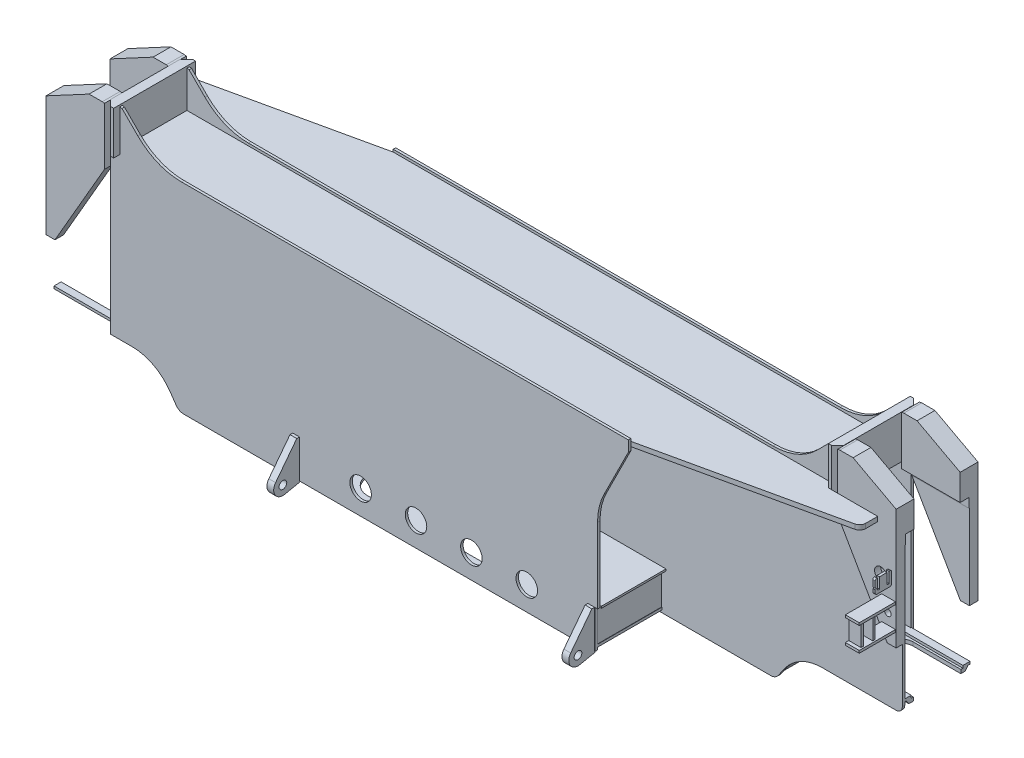
SolidWorks part; units mm, degrees
ref_plane "正面" through (0, 0, 0) normal (0, 0, 1) x (1, 0, 0)
ref_plane "平面" through (0, 0, 0) normal (0, 1, 0) x (1, 0, 0)
ref_plane "右側面" through (0, 0, 0) normal (1, 0, 0) x (0, 0, -1)
ref_plane "平面1" through (0, 0, 238) normal (0, 0, 1) x (1, 0, 0)
sketch "ｽｹｯﾁ2" plane through (0, 0, 238) normal (0, 0, 1) x (1, 0, 0)
  line L0 (20, 120) -> (259.781, 119.9998)
  line L1 (382.7741, 55.8641) -> (403.0452, 26.8271)
  line L2 (427.644, 13.9998) -> (2117.356, 13.9998)
  line L3 (2141.9548, 26.8271) -> (2162.2259, 55.8641)
  line L4 (2285.219, 119.9998) -> (2525, 120)
  line L5 (2545, 140) -> (2545, 315.36)
  line L6 (2545, 315.36) -> (2545, 706)
  line L7 (2545, 706) -> (2405, 781)
  line L8 (2405, 781) -> (2362, 781)
  line L9 (2362, 781) -> (2318, 774)
  line L10 (2318, 774) -> (2266.5789, 722.5791)
  line L11 (2125.157, 663.9999) -> (419.843, 663.9999)
  line L12 (278.4211, 722.5791) -> (227, 774)
  line L13 (227, 774) -> (183, 781)
  line L14 (183, 781) -> (140, 781)
  line L15 (140, 781) -> (0, 706)
  line L16 (0, 706) -> (0, 315.36)
  line L17 (0, 315.36) -> (0, 140)
  arc A0 (0, 140) -> (20, 120) centre (20, 140) ccw
  arc A1 (259.781, 119.9998) -> (382.7741, 55.8641) centre (259.781, -30) cw
  arc A2 (403.0452, 26.8271) -> (427.644, 13.9998) centre (427.644, 44) ccw
  arc A3 (2117.356, 13.9998) -> (2141.9548, 26.8271) centre (2117.356, 44) ccw
  arc A4 (2162.2259, 55.8641) -> (2285.219, 119.9998) centre (2285.219, -30) cw
  arc A5 (2525, 120) -> (2545, 140) centre (2525, 140) ccw
  arc A6 (2266.5789, 722.5791) -> (2125.157, 663.9999) centre (2125.157, 864) cw
  arc A7 (419.843, 663.9999) -> (278.4211, 722.5791) centre (419.843, 864) cw
extrude "ﾎﾞｽ - 押し出し1" add sketch "ｽｹｯﾁ2" along normal blind 8
sketch "ｽｹｯﾁ3" plane through (0, 0, 238) normal (0, 0, 1) x (1, 0, 0)
  line L0 (1072.5, 297) -> (1472.5, 297)
  line L1 (1472.5, 497) -> (1072.5, 497)
  circle A0 centre (972.5, 92) radius 35
  circle A1 centre (1272.5, 92) radius 35
  circle A2 centre (1572.5, 92) radius 35
  arc A3 (1472.5, 297) -> (1572.5, 397) centre (1472.5, 397) ccw
  arc A4 (1572.5, 397) -> (1472.5, 497) centre (1472.5, 397) ccw
  arc A5 (1072.5, 497) -> (972.5, 397) centre (1072.5, 397) ccw
  arc A6 (972.5, 397) -> (1072.5, 297) centre (1072.5, 397) ccw
sketch "ｽｹｯﾁ4" plane through (0, 0, 238) normal (0, 0, 1) x (1, 0, 0)
  line L0 (1072.5, 297) -> (1472.5, 297)
  line L1 (1472.5, 497) -> (1072.5, 497)
  circle A0 centre (972.5, 92) radius 35
  circle A1 centre (1272.5, 92) radius 35
  circle A2 centre (1572.5, 92) radius 35
  arc A3 (1472.5, 297) -> (1572.5, 397) centre (1472.5, 397) ccw
  arc A4 (1572.5, 397) -> (1472.5, 497) centre (1472.5, 397) ccw
  arc A5 (1072.5, 497) -> (972.5, 397) centre (1072.5, 397) ccw
  arc A6 (972.5, 397) -> (1072.5, 297) centre (1072.5, 397) ccw
extrude "ｶｯﾄ - 押し出し2" cut sketch "ｽｹｯﾁ4" along normal blind 8
ref_plane "平面2" through (0, 0, 20) normal (0, 0, 1) x (1, 0, 0)
sketch "ｽｹｯﾁ6" plane through (0, 0, 20) normal (0, 0, 1) x (1, 0, 0)
  line L0 (781, 14) -> (2117.356, 13.9998)
  line L1 (2141.9548, 26.8271) -> (2162.2259, 55.8641)
  line L2 (2285.219, 119.9998) -> (2355, 120)
  line L3 (2355, 120) -> (2355, 779.8864)
  line L4 (2355, 779.8864) -> (2318, 774)
  line L5 (2318, 774) -> (2266.5789, 722.5791)
  line L6 (2125.157, 663.9999) -> (672.5, 664)
  line L7 (672.5, 664) -> (672.5, 629)
  line L8 (672.5, 629) -> (751.3851, 471.2291)
  line L9 (772.4999, 381.786) -> (772.5, 138)
  line L10 (772.5, 138) -> (781, 138)
  line L11 (781, 138) -> (781, 14)
  arc A0 (2117.356, 13.9998) -> (2141.9548, 26.8271) centre (2117.356, 44) ccw
  arc A1 (2162.2259, 55.8641) -> (2285.219, 119.9998) centre (2285.219, -30) cw
  arc A2 (2266.5789, 722.5791) -> (2125.157, 663.9999) centre (2125.157, 864) cw
  arc A3 (751.3851, 471.2291) -> (772.4999, 381.786) centre (572.5, 381.786) cw
extrude "ﾎﾞｽ - 押し出し2" add sketch "ｽｹｯﾁ6" along normal blind 8
sketch "ｽｹｯﾁ7" plane through (0, 0, 20) normal (0, 0, 1) x (1, 0, 0)
  circle A0 centre (1002.5, 92) radius 35
  circle A1 centre (1182.5, 92) radius 35
  circle A2 centre (1362.5, 92) radius 35
  circle A3 centre (1542.5, 92) radius 35
sketch "ｽｹｯﾁ8" plane through (0, 0, 20) normal (0, 0, 1) x (1, 0, 0)
  circle A0 centre (1002.5, 92) radius 35
  circle A1 centre (1182.5, 92) radius 35
  circle A2 centre (1362.5, 92) radius 35
  circle A3 centre (1542.5, 92) radius 35
extrude "ｶｯﾄ - 押し出し4" cut sketch "ｽｹｯﾁ8" along normal blind 8
ref_plane "平面3" through (0, 0, 456) normal (0, 0, 1) x (1, 0, 0)
sketch "ｽｹｯﾁ10" plane through (0, 0, 456) normal (0, 0, 1) x (1, 0, 0)
  line L0 (1764, 14) -> (1764, 138)
  line L1 (1764, 138) -> (1772.5, 138)
  line L2 (1772.5, 138) -> (1772.5001, 381.786)
  line L3 (1793.6149, 471.2291) -> (1872.5, 629)
  line L4 (1872.5, 629) -> (1872.5, 664)
  line L5 (1872.5, 664) -> (419.843, 663.9999)
  line L6 (278.4211, 722.5791) -> (227, 774)
  line L7 (227, 774) -> (190, 779.8864)
  line L8 (190, 779.8864) -> (190, 120)
  line L9 (190, 120) -> (259.781, 119.9998)
  line L10 (382.7741, 55.8641) -> (403.0452, 26.8271)
  line L11 (427.644, 13.9998) -> (1764, 14)
  arc A0 (1772.5001, 381.786) -> (1793.6149, 471.2291) centre (1972.5, 381.786) cw
  arc A1 (419.843, 663.9999) -> (278.4211, 722.5791) centre (419.843, 864) cw
  arc A2 (259.781, 119.9998) -> (382.7741, 55.8641) centre (259.781, -30) cw
  arc A3 (403.0452, 26.8271) -> (427.644, 13.9998) centre (427.644, 44) ccw
extrude "ﾎﾞｽ - 押し出し3" add sketch "ｽｹｯﾁ10" along normal blind 8
sketch "ｽｹｯﾁ11" plane through (0, 0, 456) normal (0, 0, 1) x (1, 0, 0)
  circle A0 centre (1002.5, 92) radius 35
  circle A1 centre (1182.5, 92) radius 35
  circle A2 centre (1362.5, 92) radius 35
  circle A3 centre (1542.5, 92) radius 35
sketch "ｽｹｯﾁ12" plane through (0, 0, 456) normal (0, 0, 1) x (1, 0, 0)
  circle A0 centre (1002.5, 92) radius 35
  circle A1 centre (1182.5, 92) radius 35
  circle A2 centre (1362.5, 92) radius 35
  circle A3 centre (1542.5, 92) radius 35
extrude "ｶｯﾄ - 押し出し6" cut sketch "ｽｹｯﾁ12" along normal blind 8
ref_plane "平面4" through (0, 641, 0) normal (0, 1, 0) x (1, 0, 0)
sketch "ｽｹｯﾁ14" plane through (0, 641, 0) normal (0, 1, 0) x (1, 0, 0)
  line L0 (672.5, -28) -> (75.7206, -159.5325)
  line L1 (59.9974, -179.072) -> (60, -218)
  line L2 (60, -218) -> (220, -218)
  line L3 (220, -218) -> (220, -238)
  line L4 (220, -238) -> (2324.98, -238)
  line L5 (2324.98, -238) -> (2324.98, -28)
  line L6 (2324.98, -28) -> (672.5, -28)
  arc A0 (75.7206, -159.5325) -> (59.9974, -179.072) centre (80, -179.072) ccw
extrude "ﾎﾞｽ - 押し出し4" add sketch "ｽｹｯﾁ14" along normal blind 15
sketch "ｽｹｯﾁ15" plane through (0, 641, 0) normal (0, 1, 0) x (1, 0, 0)
  line L0 (1872.5, -456) -> (2469.2794, -324.4675)
  line L1 (2485.0026, -304.928) -> (2485, -266)
  line L2 (2485, -266) -> (2325, -266)
  line L3 (2325, -266) -> (2325, -246)
  line L4 (2325, -246) -> (220.02, -246)
  line L5 (220.02, -246) -> (220.02, -456)
  line L6 (220.02, -456) -> (1872.5, -456)
  arc A0 (2469.2794, -324.4675) -> (2485.0026, -304.928) centre (2465, -304.928) ccw
extrude "ﾎﾞｽ - 押し出し5" add sketch "ｽｹｯﾁ15" along normal blind 15
ref_plane "平面5" through (0, 22, 0) normal (0, 1, 0) x (1, 0, 0)
sketch "ｽｹｯﾁ17" plane through (0, 22, 0) normal (0, 1, 0) x (1, 0, 0)
  line L0 (781, -28) -> (2098.5, -28)
  line L1 (2098.5, -28) -> (2098.5, -238)
  line L2 (2098.5, -238) -> (781, -238)
  line L3 (781, -238) -> (781, -28)
extrude "ﾎﾞｽ - 押し出し6" add sketch "ｽｹｯﾁ17" along normal blind 8
sketch "ｽｹｯﾁ18" plane through (0, 22, 0) normal (0, 1, 0) x (1, 0, 0)
  line L0 (1202, -73) -> (1342, -73)
  line L1 (1342, -193) -> (1202, -193)
  circle A0 centre (972, -133) radius 60
  circle A1 centre (1572, -133) radius 60
  circle A2 centre (1942, -133) radius 60
  arc A3 (1342, -73) -> (1402, -133) centre (1342, -133) cw
  arc A4 (1402, -133) -> (1342, -193) centre (1342, -133) cw
  arc A5 (1202, -193) -> (1142, -133) centre (1202, -133) cw
  arc A6 (1142, -133) -> (1202, -73) centre (1202, -133) cw
sketch "ｽｹｯﾁ19" plane through (0, 22, 0) normal (0, 1, 0) x (1, 0, 0)
  line L0 (1202, -73) -> (1342, -73)
  line L1 (1342, -193) -> (1202, -193)
  circle A0 centre (972, -133) radius 60
  circle A1 centre (1572, -133) radius 60
  circle A2 centre (1942, -133) radius 60
  arc A3 (1342, -73) -> (1402, -133) centre (1342, -133) cw
  arc A4 (1402, -133) -> (1342, -193) centre (1342, -133) cw
  arc A5 (1202, -193) -> (1142, -133) centre (1202, -133) cw
  arc A6 (1142, -133) -> (1202, -73) centre (1202, -133) cw
extrude "ｶｯﾄ - 押し出し8" cut sketch "ｽｹｯﾁ19" along normal blind 8
sketch "ｽｹｯﾁ20" plane through (0, 22, 0) normal (0, 1, 0) x (1, 0, 0)
  line L0 (446.5, -246) -> (1764, -246)
  line L1 (1764, -246) -> (1764, -456)
  line L2 (1764, -456) -> (446.5, -456)
  line L3 (446.5, -456) -> (446.5, -246)
extrude "ﾎﾞｽ - 押し出し7" add sketch "ｽｹｯﾁ20" along normal blind 8
sketch "ｽｹｯﾁ21" plane through (0, 22, 0) normal (0, 1, 0) x (1, 0, 0)
  line L0 (1203, -291) -> (1343, -291)
  line L1 (1343, -411) -> (1203, -411)
  circle A0 centre (603, -351) radius 60
  circle A1 centre (973, -351) radius 60
  circle A2 centre (1573, -351) radius 60
  arc A3 (1343, -291) -> (1403, -351) centre (1343, -351) cw
  arc A4 (1403, -351) -> (1343, -411) centre (1343, -351) cw
  arc A5 (1203, -411) -> (1143, -351) centre (1203, -351) cw
  arc A6 (1143, -351) -> (1203, -291) centre (1203, -351) cw
extrude "ｶｯﾄ - 押し出し9" cut sketch "ｽｹｯﾁ21" along normal blind 8
ref_plane "平面6" through (1771.5, 0, 0) normal (1, 0, 0) x (0, 0, -1)
sketch "ｽｹｯﾁ23" plane through (1771.5, 0, 0) normal (1, 0, 0) x (0, 0, -1)
  line L0 (-27.7635, 29) -> (-40.0837, 28.97)
  line L1 (-40.0837, 28.97) -> (-63.75, 129.12)
  line L2 (-63.75, 129.12) -> (-53.77, 137.8)
  line L3 (-53.77, 137.8) -> (-53.4927, 137.8)
  line L4 (-53.4927, 137.8) -> (-27.7635, 29)
extrude "ﾎﾞｽ - 押し出し8" add sketch "ｽｹｯﾁ23" along normal blind 319
sketch "ｽｹｯﾁ24" plane through (1771.5, 0, 0) normal (1, 0, 0) x (0, 0, -1)
  line L0 (-212.5073, 137.8) -> (-212.23, 137.8)
  line L1 (-212.23, 137.8) -> (-202.25, 129.12)
  line L2 (-202.25, 129.12) -> (-225.9163, 28.97)
  line L3 (-225.9163, 28.97) -> (-238.2365, 29)
  line L4 (-238.2365, 29) -> (-212.5073, 137.8)
extrude "ﾎﾞｽ - 押し出し9" add sketch "ｽｹｯﾁ24" along normal blind 319
ref_plane "平面7" through (454.5, 0, 0) normal (1, 0, 0) x (0, 0, -1)
sketch "ｽｹｯﾁ26" plane through (454.5, 0, 0) normal (1, 0, 0) x (0, 0, -1)
  line L0 (-430.5073, 137.8) -> (-430.23, 137.8)
  line L1 (-430.23, 137.8) -> (-420.25, 129.12)
  line L2 (-420.25, 129.12) -> (-443.9163, 28.97)
  line L3 (-443.9163, 28.97) -> (-456.2365, 29)
  line L4 (-456.2365, 29) -> (-430.5073, 137.8)
extrude "ﾎﾞｽ - 押し出し10" add sketch "ｽｹｯﾁ26" along normal blind 319
sketch "ｽｹｯﾁ27" plane through (454.5, 0, 0) normal (1, 0, 0) x (0, 0, -1)
  line L0 (-245.7635, 29) -> (-258.0837, 28.97)
  line L1 (-258.0837, 28.97) -> (-281.75, 129.12)
  line L2 (-281.75, 129.12) -> (-271.77, 137.8)
  line L3 (-271.77, 137.8) -> (-271.4927, 137.8)
  line L4 (-271.4927, 137.8) -> (-245.7635, 29)
extrude "ﾎﾞｽ - 押し出し11" add sketch "ｽｹｯﾁ27" along normal blind 319
ref_plane "平面8" through (0, 138, 0) normal (0, 1, 0) x (1, 0, 0)
sketch "ｽｹｯﾁ29" plane through (0, 138, 0) normal (0, 1, 0) x (1, 0, 0)
  line L0 (768, -28) -> (1712, -28)
  line L1 (1712, -28) -> (1712, -238)
  line L2 (1712, -238) -> (768, -238)
  line L3 (768, -238) -> (768, -28)
extrude "ﾎﾞｽ - 押し出し12" add sketch "ｽｹｯﾁ29" along normal blind 6
sketch "ｽｹｯﾁ30" plane through (0, 138, 0) normal (0, 1, 0) x (1, 0, 0)
  line L0 (833, -246) -> (1777, -246)
  line L1 (1777, -246) -> (1777, -456)
  line L2 (1777, -456) -> (833, -456)
  line L3 (833, -456) -> (833, -246)
extrude "ﾎﾞｽ - 押し出し13" add sketch "ｽｹｯﾁ30" along normal blind 6
ref_plane "平面9" through (427.5, 0, 0) normal (1, 0, 0) x (0, 0, -1)
sketch "ｽｹｯﾁ32" plane through (427.5, 0, 0) normal (1, 0, 0) x (0, 0, -1)
  line L0 (-244, 22) -> (-458, 22)
  line L1 (-458, 22) -> (-458, 138)
  line L2 (-458, 138) -> (-244, 138)
  line L3 (-244, 138) -> (-244, 22)
extrude "ﾎﾞｽ - 押し出し14" add sketch "ｽｹｯﾁ32" along normal blind 19
sketch "ｽｹｯﾁ33" plane through (427.5, 0, 0) normal (1, 0, 0) x (0, 0, -1)
  circle A0 centre (-351, 80) radius 30
sketch "ｽｹｯﾁ34" plane through (427.5, 0, 0) normal (1, 0, 0) x (0, 0, -1)
  circle A0 centre (-351, 80) radius 30
extrude "ｶｯﾄ - 押し出し11" cut sketch "ｽｹｯﾁ34" along normal blind 19
ref_plane "平面10" through (2098.5, 0, 0) normal (1, 0, 0) x (0, 0, -1)
sketch "ｽｹｯﾁ36" plane through (2098.5, 0, 0) normal (1, 0, 0) x (0, 0, -1)
  line L0 (-26, 22) -> (-240, 22)
  line L1 (-240, 22) -> (-240, 138)
  line L2 (-240, 138) -> (-26, 138)
  line L3 (-26, 138) -> (-26, 22)
extrude "ﾎﾞｽ - 押し出し15" add sketch "ｽｹｯﾁ36" along normal blind 19
sketch "ｽｹｯﾁ37" plane through (2098.5, 0, 0) normal (1, 0, 0) x (0, 0, -1)
  circle A0 centre (-133, 80) radius 30
sketch "ｽｹｯﾁ38" plane through (2098.5, 0, 0) normal (1, 0, 0) x (0, 0, -1)
  circle A0 centre (-133, 80) radius 30
extrude "ｶｯﾄ - 押し出し13" cut sketch "ｽｹｯﾁ38" along normal blind 19
ref_plane "平面11" through (0, 0, 218) normal (0, 0, 1) x (1, 0, 0)
sketch "ｽｹｯﾁ40" plane through (0, 0, 218) normal (0, 0, 1) x (1, 0, 0)
  line L0 (0, 315.36) -> (29.1052, 315.36)
  line L1 (29.1052, 315.36) -> (190, 594.038)
  line L2 (190, 594.038) -> (190, 779.8864)
  line L3 (190, 779.8864) -> (183, 781)
  line L4 (183, 781) -> (140, 781)
  line L5 (140, 781) -> (0, 706)
  line L6 (0, 706) -> (0, 315.36)
extrude "ﾎﾞｽ - 押し出し16" add sketch "ｽｹｯﾁ40" along normal blind 20
ref_plane "平面12" through (0, 0, 464) normal (0, 0, 1) x (1, 0, 0)
sketch "ｽｹｯﾁ42" plane through (0, 0, 464) normal (0, 0, 1) x (1, 0, 0)
  line L0 (0, 315.36) -> (29.1052, 315.36)
  line L1 (29.1052, 315.36) -> (190, 594.038)
  line L2 (190, 594.038) -> (190, 779.8864)
  line L3 (190, 779.8864) -> (183, 781)
  line L4 (183, 781) -> (140, 781)
  line L5 (140, 781) -> (0, 706)
  line L6 (0, 706) -> (0, 315.36)
extrude "ﾎﾞｽ - 押し出し17" add sketch "ｽｹｯﾁ42" along normal blind 20
sketch "ｽｹｯﾁ43" plane through (0, 0, 0) normal (0, 0, 1) x (1, 0, 0)
  line L0 (2545, 315.36) -> (2545, 706)
  line L1 (2545, 706) -> (2405, 781)
  line L2 (2405, 781) -> (2362, 781)
  line L3 (2362, 781) -> (2355, 779.8864)
  line L4 (2355, 779.8864) -> (2355, 594.038)
  line L5 (2355, 594.038) -> (2515.8948, 315.36)
  line L6 (2515.8948, 315.36) -> (2545, 315.36)
extrude "ﾎﾞｽ - 押し出し18" add sketch "ｽｹｯﾁ43" along normal blind 20
ref_plane "平面13" through (0, 0, 246) normal (0, 0, 1) x (1, 0, 0)
sketch "ｽｹｯﾁ45" plane through (0, 0, 246) normal (0, 0, 1) x (1, 0, 0)
  line L0 (2545, 315.36) -> (2545, 706)
  line L1 (2545, 706) -> (2405, 781)
  line L2 (2405, 781) -> (2362, 781)
  line L3 (2362, 781) -> (2355, 779.8864)
  line L4 (2355, 779.8864) -> (2355, 594.038)
  line L5 (2355, 594.038) -> (2515.8948, 315.36)
  line L6 (2515.8948, 315.36) -> (2545, 315.36)
extrude "ﾎﾞｽ - 押し出し19" add sketch "ｽｹｯﾁ45" along normal blind 20
sketch "ｽｹｯﾁ46" plane through (0, 0, 218) normal (0, 0, 1) x (1, 0, 0)
  circle A0 centre (50, 499) radius 20.25
  circle A1 centre (27, 401.5) radius 10.5
sketch "ｽｹｯﾁ47" plane through (0, 0, 218) normal (0, 0, 1) x (1, 0, 0)
  circle A0 centre (50, 499) radius 20.25
  circle A1 centre (27, 401.5) radius 10.5
extrude "ｶｯﾄ - 押し出し15" cut sketch "ｽｹｯﾁ47" along normal blind 20
sketch "ｽｹｯﾁ48" plane through (0, 0, 246) normal (0, 0, 1) x (1, 0, 0)
  circle A0 centre (2495, 499) radius 20.25
  circle A1 centre (2518, 401.5) radius 10.5
sketch "ｽｹｯﾁ49" plane through (0, 0, 246) normal (0, 0, 1) x (1, 0, 0)
  circle A0 centre (2495, 499) radius 20.25
  circle A1 centre (2518, 401.5) radius 10.5
extrude "ｶｯﾄ - 押し出し17" cut sketch "ｽｹｯﾁ49" along normal blind 20
sketch "ｽｹｯﾁ50" plane through (0, 0, 20) normal (0, 0, 1) x (1, 0, 0)
  line L0 (2545, 315.36) -> (2545, 706)
  line L1 (2545, 706) -> (2405, 781)
  line L2 (2405, 781) -> (2362, 781)
  line L3 (2362, 781) -> (2355, 779.8864)
  line L4 (2355, 779.8864) -> (2355, 594.038)
  line L5 (2355, 594.038) -> (2515.8948, 315.36)
  line L6 (2515.8948, 315.36) -> (2545, 315.36)
extrude "ﾎﾞｽ - 押し出し20" add sketch "ｽｹｯﾁ50" along normal blind 8
sketch "ｽｹｯﾁ51" plane through (0, 0, 456) normal (0, 0, 1) x (1, 0, 0)
  line L0 (0, 315.36) -> (29.1052, 315.36)
  line L1 (29.1052, 315.36) -> (190, 594.038)
  line L2 (190, 594.038) -> (190, 779.8864)
  line L3 (190, 779.8864) -> (183, 781)
  line L4 (183, 781) -> (140, 781)
  line L5 (140, 781) -> (0, 706)
  line L6 (0, 706) -> (0, 315.36)
extrude "ﾎﾞｽ - 押し出し21" add sketch "ｽｹｯﾁ51" along normal blind 8
ref_plane "平面14" through (0, 0, 251) normal (0, 0, 1) x (1, 0, 0)
sketch "ｽｹｯﾁ53" plane through (0, 0, 251) normal (0, 0, 1) x (1, 0, 0)
  line L0 (0, 620.82) -> (190, 620.82)
  line L1 (190, 620.82) -> (190, 779.8864)
  line L2 (190, 779.8864) -> (183, 781)
  line L3 (183, 781) -> (140, 781)
  line L4 (140, 781) -> (0, 706)
  line L5 (0, 706) -> (0, 620.82)
extrude "ﾎﾞｽ - 押し出し22" add sketch "ｽｹｯﾁ53" along normal blind 25
ref_plane "平面15" through (0, 0, 426) normal (0, 0, 1) x (1, 0, 0)
sketch "ｽｹｯﾁ55" plane through (0, 0, 426) normal (0, 0, 1) x (1, 0, 0)
  line L0 (0, 620.82) -> (190, 620.82)
  line L1 (190, 620.82) -> (190, 779.8864)
  line L2 (190, 779.8864) -> (183, 781)
  line L3 (183, 781) -> (140, 781)
  line L4 (140, 781) -> (0, 706)
  line L5 (0, 706) -> (0, 620.82)
extrude "ﾎﾞｽ - 押し出し23" add sketch "ｽｹｯﾁ55" along normal blind 25
ref_plane "平面16" through (0, 0, 33) normal (0, 0, 1) x (1, 0, 0)
sketch "ｽｹｯﾁ57" plane through (0, 0, 33) normal (0, 0, 1) x (1, 0, 0)
  line L0 (2545, 620.82) -> (2545, 706)
  line L1 (2545, 706) -> (2405, 781)
  line L2 (2405, 781) -> (2362, 781)
  line L3 (2362, 781) -> (2355, 779.8864)
  line L4 (2355, 779.8864) -> (2355, 620.82)
  line L5 (2355, 620.82) -> (2545, 620.82)
extrude "ﾎﾞｽ - 押し出し24" add sketch "ｽｹｯﾁ57" along normal blind 25
ref_plane "平面17" through (0, 0, 208) normal (0, 0, 1) x (1, 0, 0)
sketch "ｽｹｯﾁ59" plane through (0, 0, 208) normal (0, 0, 1) x (1, 0, 0)
  line L0 (2545, 620.82) -> (2545, 706)
  line L1 (2545, 706) -> (2405, 781)
  line L2 (2405, 781) -> (2362, 781)
  line L3 (2362, 781) -> (2355, 779.8864)
  line L4 (2355, 779.8864) -> (2355, 620.82)
  line L5 (2355, 620.82) -> (2545, 620.82)
extrude "ﾎﾞｽ - 押し出し25" add sketch "ｽｹｯﾁ59" along normal blind 25
ref_plane "平面18" through (0, 0, 244) normal (0, 0, 1) x (1, 0, 0)
sketch "ｽｹｯﾁ61" plane through (0, 0, 244) normal (0, 0, 1) x (1, 0, 0)
  line L0 (0, 620.82) -> (190, 620.82)
  line L1 (190, 620.82) -> (190, 779.8864)
  line L2 (190, 779.8864) -> (183, 781)
  line L3 (183, 781) -> (140, 781)
  line L4 (140, 781) -> (0, 706)
  line L5 (0, 706) -> (0, 620.82)
extrude "ﾎﾞｽ - 押し出し26" add sketch "ｽｹｯﾁ61" along normal blind 7
sketch "ｽｹｯﾁ62" plane through (0, 0, 244) normal (0, 0, 1) x (1, 0, 0)
  line L0 (0, 590.821) -> (188.1427, 590.821)
  line L1 (188.1427, 590.821) -> (190, 594.038)
  line L2 (190, 594.038) -> (190, 620.82)
  line L3 (190, 620.82) -> (0, 620.82)
  line L4 (0, 620.82) -> (0, 590.821)
extrude "ﾎﾞｽ - 押し出し27" add sketch "ｽｹｯﾁ62" along normal blind 4
ref_plane "平面19" through (0, 0, 451) normal (0, 0, 1) x (1, 0, 0)
sketch "ｽｹｯﾁ64" plane through (0, 0, 451) normal (0, 0, 1) x (1, 0, 0)
  line L0 (0, 620.82) -> (190, 620.82)
  line L1 (190, 620.82) -> (190, 779.8864)
  line L2 (190, 779.8864) -> (183, 781)
  line L3 (183, 781) -> (140, 781)
  line L4 (140, 781) -> (0, 706)
  line L5 (0, 706) -> (0, 620.82)
extrude "ﾎﾞｽ - 押し出し28" add sketch "ｽｹｯﾁ64" along normal blind 7
ref_plane "平面20" through (0, 0, 454) normal (0, 0, 1) x (1, 0, 0)
sketch "ｽｹｯﾁ66" plane through (0, 0, 454) normal (0, 0, 1) x (1, 0, 0)
  line L0 (0, 590.821) -> (188.1427, 590.821)
  line L1 (188.1427, 590.821) -> (190, 594.038)
  line L2 (190, 594.038) -> (190, 620.82)
  line L3 (190, 620.82) -> (0, 620.82)
  line L4 (0, 620.82) -> (0, 590.821)
extrude "ﾎﾞｽ - 押し出し29" add sketch "ｽｹｯﾁ66" along normal blind 4
ref_plane "平面21" through (0, 0, 26) normal (0, 0, 1) x (1, 0, 0)
sketch "ｽｹｯﾁ68" plane through (0, 0, 26) normal (0, 0, 1) x (1, 0, 0)
  line L0 (2545, 620.82) -> (2545, 706)
  line L1 (2545, 706) -> (2405, 781)
  line L2 (2405, 781) -> (2362, 781)
  line L3 (2362, 781) -> (2355, 779.8864)
  line L4 (2355, 779.8864) -> (2355, 620.82)
  line L5 (2355, 620.82) -> (2545, 620.82)
extrude "ﾎﾞｽ - 押し出し30" add sketch "ｽｹｯﾁ68" along normal blind 7
sketch "ｽｹｯﾁ69" plane through (0, 0, 26) normal (0, 0, 1) x (1, 0, 0)
  line L0 (2545, 590.821) -> (2545, 620.82)
  line L1 (2545, 620.82) -> (2355, 620.82)
  line L2 (2355, 620.82) -> (2355, 594.038)
  line L3 (2355, 594.038) -> (2356.8573, 590.821)
  line L4 (2356.8573, 590.821) -> (2545, 590.821)
extrude "ﾎﾞｽ - 押し出し31" add sketch "ｽｹｯﾁ69" along normal blind 4
ref_plane "平面22" through (0, 0, 233) normal (0, 0, 1) x (1, 0, 0)
sketch "ｽｹｯﾁ71" plane through (0, 0, 233) normal (0, 0, 1) x (1, 0, 0)
  line L0 (2545, 620.82) -> (2545, 706)
  line L1 (2545, 706) -> (2405, 781)
  line L2 (2405, 781) -> (2362, 781)
  line L3 (2362, 781) -> (2355, 779.8864)
  line L4 (2355, 779.8864) -> (2355, 620.82)
  line L5 (2355, 620.82) -> (2545, 620.82)
extrude "ﾎﾞｽ - 押し出し32" add sketch "ｽｹｯﾁ71" along normal blind 7
ref_plane "平面23" through (0, 0, 236) normal (0, 0, 1) x (1, 0, 0)
sketch "ｽｹｯﾁ73" plane through (0, 0, 236) normal (0, 0, 1) x (1, 0, 0)
  line L0 (2545, 590.821) -> (2545, 620.82)
  line L1 (2545, 620.82) -> (2355, 620.82)
  line L2 (2355, 620.82) -> (2355, 594.038)
  line L3 (2355, 594.038) -> (2356.8573, 590.821)
  line L4 (2356.8573, 590.821) -> (2545, 590.821)
extrude "ﾎﾞｽ - 押し出し33" add sketch "ｽｹｯﾁ73" along normal blind 4
sketch "ｽｹｯﾁ74" plane through (0, 0, 0) normal (1, 0, 0) x (0, 0, -1)
  line L0 (-251.6, 150) -> (-450.4, 150)
  line L1 (-450.4, 150) -> (-450.4, 149)
  line L2 (-450.4, 149) -> (-442.698, 138)
  line L3 (-442.698, 138) -> (-259.302, 138)
  line L4 (-259.302, 138) -> (-251.6, 149)
  line L5 (-251.6, 149) -> (-251.6, 150)
extrude "ﾎﾞｽ - 押し出し34" add sketch "ｽｹｯﾁ74" along normal blind 833
sketch "ｽｹｯﾁ75" plane through (0, 138, 0) normal (0, 1, 0) x (1, 0, 0)
  line L0 (-10, -273.771) -> (155, -273.771)
  line L1 (195, -313.771) -> (195, -388.229)
  line L2 (155, -428.229) -> (-10, -428.229)
  line L3 (-10, -428.229) -> (-10, -273.771)
  arc A0 (155, -273.771) -> (195, -313.771) centre (155, -313.771) cw
  arc A1 (195, -388.229) -> (155, -428.229) centre (155, -388.229) cw
sketch "ｽｹｯﾁ76" plane through (0, 138, 0) normal (0, 1, 0) x (1, 0, 0)
  line L0 (-10, -273.771) -> (155, -273.771)
  line L1 (195, -313.771) -> (195, -388.229)
  line L2 (155, -428.229) -> (-10, -428.229)
  line L3 (-10, -428.229) -> (-10, -273.771)
  arc A0 (155, -273.771) -> (195, -313.771) centre (155, -313.771) cw
  arc A1 (195, -388.229) -> (155, -428.229) centre (155, -388.229) cw
extrude "ｶｯﾄ - 押し出し19" cut sketch "ｽｹｯﾁ76" along normal blind 12
ref_plane "平面24" through (2545, 0, 0) normal (1, 0, 0) x (0, 0, -1)
sketch "ｽｹｯﾁ78" plane through (2545, 0, 0) normal (1, 0, 0) x (0, 0, -1)
  line L0 (-232.4, 150) -> (-232.4, 149)
  line L1 (-232.4, 149) -> (-224.698, 138)
  line L2 (-224.698, 138) -> (-41.302, 138)
  line L3 (-41.302, 138) -> (-33.6, 149)
  line L4 (-33.6, 149) -> (-33.6, 150)
  line L5 (-33.6, 150) -> (-232.4, 150)
extrude "ﾎﾞｽ - 押し出し35" add sketch "ｽｹｯﾁ78" against normal blind 833
sketch "ｽｹｯﾁ79" plane through (0, 138, 0) normal (0, 1, 0) x (1, 0, 0)
  line L0 (2555, -210.229) -> (2390, -210.229)
  line L1 (2350, -170.229) -> (2350, -95.771)
  line L2 (2390, -55.771) -> (2555, -55.771)
  line L3 (2555, -55.771) -> (2555, -210.229)
  arc A0 (2390, -210.229) -> (2350, -170.229) centre (2390, -170.229) cw
  arc A1 (2350, -95.771) -> (2390, -55.771) centre (2390, -95.771) cw
extrude "ｶｯﾄ - 押し出し20" cut sketch "ｽｹｯﾁ79" along normal blind 12
ref_plane "平面25" through (0, 150, 0) normal (0, 1, 0) x (1, 0, 0)
sketch "ｽｹｯﾁ81" plane through (0, 150, 0) normal (0, 1, 0) x (1, 0, 0)
  line L0 (0, -244) -> (833, -244)
  line L1 (833, -244) -> (833, -291)
  line L2 (833, -291) -> (215.708, -291)
  line L3 (215.708, -291) -> (190, -267)
  line L4 (190, -267) -> (0, -267)
  line L5 (0, -267) -> (0, -244)
  line L6 (0, -458) -> (833, -458)
  line L7 (833, -458) -> (833, -411)
  line L8 (833, -411) -> (215.708, -411)
  line L9 (215.708, -411) -> (190, -435)
  line L10 (190, -435) -> (0, -435)
  line L11 (0, -435) -> (0, -458)
extrude "ﾎﾞｽ - 押し出し36" add sketch "ｽｹｯﾁ81" along normal blind 8
sketch "ｽｹｯﾁ82" plane through (0, 150, 0) normal (0, 1, 0) x (1, 0, 0)
  line L0 (2545, -240) -> (1712, -240)
  line L1 (1712, -240) -> (1712, -193)
  line L2 (1712, -193) -> (2329.292, -193)
  line L3 (2329.292, -193) -> (2355, -217)
  line L4 (2355, -217) -> (2545, -217)
  line L5 (2545, -217) -> (2545, -240)
  line L6 (2545, -26) -> (1712, -26)
  line L7 (1712, -26) -> (1712, -73)
  line L8 (1712, -73) -> (2329.292, -73)
  line L9 (2329.292, -73) -> (2355, -49)
  line L10 (2355, -49) -> (2545, -49)
  line L11 (2545, -49) -> (2545, -26)
extrude "ﾎﾞｽ - 押し出し37" add sketch "ｽｹｯﾁ82" along normal blind 8
ref_plane "平面26" through (782, 0, 0) normal (1, 0, 0) x (0, 0, -1)
sketch "ｽｹｯﾁ84" plane through (782, 0, 0) normal (1, 0, 0) x (0, 0, -1)
  line L0 (-26, 29) -> (-240, 29)
  line L1 (-240, 29) -> (-240, 138)
  line L2 (-240, 138) -> (-26, 138)
  line L3 (-26, 138) -> (-26, 29)
  line L4 (-244, 29) -> (-458, 29)
  line L5 (-458, 29) -> (-458, 138)
  line L6 (-458, 138) -> (-244, 138)
  line L7 (-244, 138) -> (-244, 29)
  line L8 (-462, 10.7792) -> (-512.0187, 0.6023)
  line L9 (-541.8079, 48.2533) -> (-473, 138)
  line L10 (-473, 138) -> (-462, 138)
  line L11 (-462, 138) -> (-462, 10.7792)
  arc A0 (-512.0187, 0.6023) -> (-541.8079, 48.2533) centre (-518, 30) cw
extrude "ﾎﾞｽ - 押し出し38" add sketch "ｽｹｯﾁ84" along normal blind 22
sketch "ｽｹｯﾁ85" plane through (782, 0, 0) normal (1, 0, 0) x (0, 0, -1)
  circle A0 centre (-518, 30) radius 12.5
sketch "ｽｹｯﾁ86" plane through (782, 0, 0) normal (1, 0, 0) x (0, 0, -1)
  circle A0 centre (-518, 30) radius 12.5
extrude "ｶｯﾄ - 押し出し22" cut sketch "ｽｹｯﾁ86" along normal blind 22
ref_plane "平面27" through (1741, 0, 0) normal (1, 0, 0) x (0, 0, -1)
sketch "ｽｹｯﾁ88" plane through (1741, 0, 0) normal (1, 0, 0) x (0, 0, -1)
  line L0 (-26, 29) -> (-240, 29)
  line L1 (-240, 29) -> (-240, 138)
  line L2 (-240, 138) -> (-26, 138)
  line L3 (-26, 138) -> (-26, 29)
  line L4 (-244, 29) -> (-458, 29)
  line L5 (-458, 29) -> (-458, 138)
  line L6 (-458, 138) -> (-244, 138)
  line L7 (-244, 138) -> (-244, 29)
  line L8 (-462, 10.7792) -> (-512.0187, 0.6023)
  line L9 (-541.8079, 48.2533) -> (-473, 138)
  line L10 (-473, 138) -> (-462, 138)
  line L11 (-462, 138) -> (-462, 10.7792)
  arc A0 (-512.0187, 0.6023) -> (-541.8079, 48.2533) centre (-518, 30) cw
extrude "ﾎﾞｽ - 押し出し39" add sketch "ｽｹｯﾁ88" along normal blind 22
sketch "ｽｹｯﾁ89" plane through (1741, 0, 0) normal (1, 0, 0) x (0, 0, -1)
  circle A0 centre (-518, 30) radius 12.5
sketch "ｽｹｯﾁ90" plane through (1741, 0, 0) normal (1, 0, 0) x (0, 0, -1)
  circle A0 centre (-518, 30) radius 12.5
extrude "ｶｯﾄ - 押し出し24" cut sketch "ｽｹｯﾁ90" along normal blind 22
ref_plane "平面28" through (2, 0, 0) normal (1, 0, 0) x (0, 0, -1)
sketch "ｽｹｯﾁ92" plane through (2, 0, 0) normal (1, 0, 0) x (0, 0, -1)
  line L0 (-100, 358.5) -> (-218, 358.5)
  line L1 (-218, 358.5) -> (-218, 366.5)
  line L2 (-218, 366.5) -> (-100, 366.5)
  line L3 (-100, 366.5) -> (-100, 358.5)
  line L4 (-100, 436.5) -> (-218, 436.5)
  line L5 (-218, 436.5) -> (-218, 444.5)
  line L6 (-218, 444.5) -> (-100, 444.5)
  line L7 (-100, 444.5) -> (-100, 436.5)
extrude "ﾎﾞｽ - 押し出し40" add sketch "ｽｹｯﾁ92" along normal blind 45
ref_plane "平面29" through (7, 0, 0) normal (1, 0, 0) x (0, 0, -1)
sketch "ｽｹｯﾁ94" plane through (7, 0, 0) normal (1, 0, 0) x (0, 0, -1)
  line L0 (-111, 366.5) -> (-119, 366.5)
  line L1 (-119, 366.5) -> (-119, 436.5)
  line L2 (-119, 436.5) -> (-111, 436.5)
  line L3 (-111, 436.5) -> (-111, 366.5)
  line L4 (-149, 366.5) -> (-157, 366.5)
  line L5 (-157, 366.5) -> (-157, 436.5)
  line L6 (-157, 436.5) -> (-149, 436.5)
  line L7 (-149, 436.5) -> (-149, 366.5)
extrude "ﾎﾞｽ - 押し出し41" add sketch "ｽｹｯﾁ94" along normal blind 40
ref_plane "平面30" through (2498, 0, 0) normal (1, 0, 0) x (0, 0, -1)
sketch "ｽｹｯﾁ96" plane through (2498, 0, 0) normal (1, 0, 0) x (0, 0, -1)
  line L0 (-266, 358.5) -> (-384, 358.5)
  line L1 (-384, 358.5) -> (-384, 366.5)
  line L2 (-384, 366.5) -> (-266, 366.5)
  line L3 (-266, 366.5) -> (-266, 358.5)
  line L4 (-266, 436.5) -> (-384, 436.5)
  line L5 (-384, 436.5) -> (-384, 444.5)
  line L6 (-384, 444.5) -> (-266, 444.5)
  line L7 (-266, 444.5) -> (-266, 436.5)
extrude "ﾎﾞｽ - 押し出し42" add sketch "ｽｹｯﾁ96" along normal blind 45
sketch "ｽｹｯﾁ97" plane through (2498, 0, 0) normal (1, 0, 0) x (0, 0, -1)
  line L0 (-365, 366.5) -> (-373, 366.5)
  line L1 (-373, 366.5) -> (-373, 436.5)
  line L2 (-373, 436.5) -> (-365, 436.5)
  line L3 (-365, 436.5) -> (-365, 366.5)
  line L4 (-327, 366.5) -> (-335, 366.5)
  line L5 (-335, 366.5) -> (-335, 436.5)
  line L6 (-335, 436.5) -> (-327, 436.5)
  line L7 (-327, 436.5) -> (-327, 366.5)
extrude "ﾎﾞｽ - 押し出し43" add sketch "ｽｹｯﾁ97" along normal blind 40
ref_plane "平面31" through (15, 0, 0) normal (1, 0, 0) x (0, 0, -1)
sketch "ｽｹｯﾁ99" plane through (15, 0, 0) normal (1, 0, 0) x (0, 0, -1)
  line L0 (-170, 483) -> (-213, 483)
  line L1 (-218, 488) -> (-218, 523)
  line L2 (-213, 528) -> (-170, 528)
  line L3 (-165, 523) -> (-165, 488)
  arc A0 (-213, 483) -> (-218, 488) centre (-213, 488) cw
  arc A1 (-218, 523) -> (-213, 528) centre (-213, 523) cw
  arc A2 (-170, 528) -> (-165, 523) centre (-170, 523) cw
  arc A3 (-165, 488) -> (-170, 483) centre (-170, 488) cw
extrude "ﾎﾞｽ - 押し出し44" add sketch "ｽｹｯﾁ99" along normal blind 8
sketch "ｽｹｯﾁ100" plane through (15, 0, 0) normal (1, 0, 0) x (0, 0, -1)
  line L0 (-172, 493) -> (-179, 493)
  line L1 (-179, 493) -> (-179, 535)
  line L2 (-179, 535) -> (-172, 535)
  line L3 (-172, 535) -> (-172, 493)
  line L4 (-203, 493) -> (-210, 493)
  line L5 (-210, 493) -> (-210, 535)
  line L6 (-210, 535) -> (-203, 535)
  line L7 (-203, 535) -> (-203, 493)
sketch "ｽｹｯﾁ101" plane through (15, 0, 0) normal (1, 0, 0) x (0, 0, -1)
  line L0 (-172, 493) -> (-179, 493)
  line L1 (-179, 493) -> (-179, 535)
  line L2 (-179, 535) -> (-172, 535)
  line L3 (-172, 535) -> (-172, 493)
  line L4 (-203, 493) -> (-210, 493)
  line L5 (-210, 493) -> (-210, 535)
  line L6 (-210, 535) -> (-203, 535)
  line L7 (-203, 535) -> (-203, 493)
extrude "ｶｯﾄ - 押し出し26" cut sketch "ｽｹｯﾁ101" along normal blind 8
sketch "ｽｹｯﾁ102" plane through (15, 0, 0) normal (1, 0, 0) x (0, 0, -1)
  circle A0 centre (-166, 500) radius 2.5
extrude "ｶｯﾄ - 押し出し27" cut sketch "ｽｹｯﾁ102" along normal blind 8
ref_plane "平面32" through (2522, 0, 0) normal (1, 0, 0) x (0, 0, -1)
sketch "ｽｹｯﾁ104" plane through (2522, 0, 0) normal (1, 0, 0) x (0, 0, -1)
  line L0 (-271, 483) -> (-314, 483)
  line L1 (-319, 488) -> (-319, 523)
  line L2 (-314, 528) -> (-271, 528)
  line L3 (-266, 523) -> (-266, 488)
  arc A0 (-314, 483) -> (-319, 488) centre (-314, 488) cw
  arc A1 (-319, 523) -> (-314, 528) centre (-314, 523) cw
  arc A2 (-271, 528) -> (-266, 523) centre (-271, 523) cw
  arc A3 (-266, 488) -> (-271, 483) centre (-271, 488) cw
extrude "ﾎﾞｽ - 押し出し45" add sketch "ｽｹｯﾁ104" along normal blind 8
sketch "ｽｹｯﾁ105" plane through (2522, 0, 0) normal (1, 0, 0) x (0, 0, -1)
  line L0 (-305, 493) -> (-312, 493)
  line L1 (-312, 493) -> (-312, 535)
  line L2 (-312, 535) -> (-305, 535)
  line L3 (-305, 535) -> (-305, 493)
  line L4 (-274, 493) -> (-281, 493)
  line L5 (-281, 493) -> (-281, 535)
  line L6 (-281, 535) -> (-274, 535)
  line L7 (-274, 535) -> (-274, 493)
sketch "ｽｹｯﾁ106" plane through (2522, 0, 0) normal (1, 0, 0) x (0, 0, -1)
  line L0 (-305, 493) -> (-312, 493)
  line L1 (-312, 493) -> (-312, 535)
  line L2 (-312, 535) -> (-305, 535)
  line L3 (-305, 535) -> (-305, 493)
  line L4 (-274, 493) -> (-281, 493)
  line L5 (-281, 493) -> (-281, 535)
  line L6 (-281, 535) -> (-274, 535)
  line L7 (-274, 535) -> (-274, 493)
extrude "ｶｯﾄ - 押し出し29" cut sketch "ｽｹｯﾁ106" along normal blind 8
sketch "ｽｹｯﾁ107" plane through (2522, 0, 0) normal (1, 0, 0) x (0, 0, -1)
  circle A0 centre (-318, 500) radius 2.5
extrude "ｶｯﾄ - 押し出し30" cut sketch "ｽｹｯﾁ107" along normal blind 8
sketch "ｽｹｯﾁ108" plane through (0, 641, 0) normal (0, 1, 0) x (1, 0, 0)
  line L0 (190, -238) -> (210, -218)
  line L1 (210, -218) -> (220, -218)
  line L2 (220, -218) -> (220, -484)
  line L3 (220, -484) -> (210, -484)
  line L4 (210, -484) -> (190, -464)
  line L5 (190, -464) -> (190, -238)
extrude "ﾎﾞｽ - 押し出し46" add sketch "ｽｹｯﾁ108" along normal blind 140
sketch "ｽｹｯﾁ109" plane through (0, 641, 0) normal (0, 1, 0) x (1, 0, 0)
  line L0 (2355, -246) -> (2335, -266)
  line L1 (2335, -266) -> (2325, -266)
  line L2 (2325, -266) -> (2325, 0)
  line L3 (2325, 0) -> (2335, 0)
  line L4 (2335, 0) -> (2355, -20)
  line L5 (2355, -20) -> (2355, -246)
extrude "ﾎﾞｽ - 押し出し47" add sketch "ｽｹｯﾁ109" along normal blind 140
ref_plane "平面33" through (0, 0, 257) normal (0, 0, 1) x (1, 0, 0)
sketch "ｽｹｯﾁ111" plane through (0, 0, 257) normal (0, 0, 1) x (1, 0, 0)
  line L0 (412.1531, 22.0886) -> (421.9829, 28.9714)
  line L1 (421.9829, 28.9714) -> (344.9409, 139)
  line L2 (344.9409, 139) -> (330.2916, 139)
  line L3 (330.2916, 139) -> (412.1531, 22.0886)
extrude "ﾎﾞｽ - 押し出し48" add sketch "ｽｹｯﾁ111" along normal blind 188
ref_plane "平面34" through (0, 0, 351) normal (0, 0, 1) x (1, 0, 0)
sketch "ｽｹｯﾁ113" plane through (0, 0, 351) normal (0, 0, 1) x (1, 0, 0)
  line L0 (359.9091, 63.5757) -> (400.8669, 92.2543)
  line L1 (400.8669, 92.2543) -> (377.924, 125.0205)
  line L2 (377.924, 125.0205) -> (336.9662, 96.3419)
  line L3 (336.9662, 96.3419) -> (359.9091, 63.5757)
  line L4 (359.9091, 63.5757) -> (400.8669, 92.2543) construction
revolve "ｶｯﾄ - 回転1" cut sketch "ｽｹｯﾁ113" angle 360 about L4
ref_plane "平面35" through (0, 0, 39) normal (0, 0, 1) x (1, 0, 0)
sketch "ｽｹｯﾁ115" plane through (0, 0, 39) normal (0, 0, 1) x (1, 0, 0)
  line L0 (2214.7084, 139) -> (2200.0591, 139)
  line L1 (2200.0591, 139) -> (2123.0171, 28.9714)
  line L2 (2123.0171, 28.9714) -> (2132.8469, 22.0886)
  line L3 (2132.8469, 22.0886) -> (2214.7084, 139)
extrude "ﾎﾞｽ - 押し出し49" add sketch "ｽｹｯﾁ115" along normal blind 188
ref_plane "平面36" through (0, 0, 133) normal (0, 0, 1) x (1, 0, 0)
sketch "ｽｹｯﾁ117" plane through (0, 0, 133) normal (0, 0, 1) x (1, 0, 0)
  line L0 (2185.0909, 63.5757) -> (2144.1331, 92.2543)
  line L1 (2144.1331, 92.2543) -> (2121.1902, 59.4881)
  line L2 (2121.1902, 59.4881) -> (2162.148, 30.8095)
  line L3 (2162.148, 30.8095) -> (2185.0909, 63.5757)
  line L4 (2185.0909, 63.5757) -> (2144.1331, 92.2543) construction
revolve "ｶｯﾄ - 回転2" cut sketch "ｽｹｯﾁ117" angle 360 about L4
